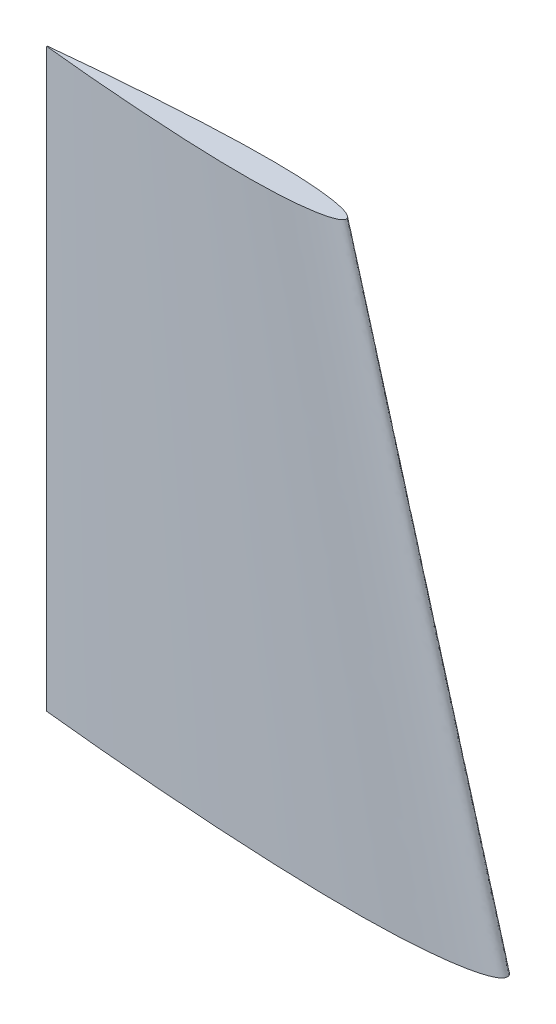
SolidWorks part; units mm, degrees
ref_plane "Front Plane" through (0, 0, 0) normal (0, 0, 1) x (1, 0, 0)
ref_plane "Top Plane" through (0, 0, 0) normal (0, 1, 0) x (1, 0, 0)
ref_plane "Right Plane" through (0, 0, 0) normal (1, 0, 0) x (0, 0, -1)
sketch "Sketch1" plane through (0, 0, 0) normal (0, 1, 0) x (1, 0, 0)
  line L0 (-150.36, 0.1421) -> (-150.36, -0.1421)
  spline S0 degree 3 poles (-150.36, 0.1421) (-150.2227, 0.1565) (-149.6751, 0.2141) (-148.4487, 0.342) (-146.4196, 0.551) (-143.6099, 0.8346) (-140.0506, 1.185) (-135.7805, 1.5925) (-130.8465, 2.0468) (-125.3025, 2.537) (-119.2094, 3.0518) (-112.6339, 3.5796) (-105.6481, 4.1088) (-98.3285, 4.6268) (-90.7552, 5.1209) (-83.0113, 5.5771) (-75.1816, 5.9812) (-67.3517, 6.3184) (-59.6075, 6.574) (-52.0337, 6.7344) (-44.7132, 6.7875) (-37.7261, 6.7242) (-31.1488, 6.5386) (-25.0534, 6.229) (-19.5062, 5.7981) (-14.5678, 5.2523) (-10.2903, 4.6034) (-6.7204, 3.8615) (-3.8842, 3.0521) (-1.8121, 2.1635) (-0.4317, 1.2454) (0.1785, 0) (-0.4317, -1.2454) (-1.8121, -2.1635) (-3.8842, -3.0521) (-6.7204, -3.8615) (-10.2903, -4.6034) (-14.5678, -5.2523) (-19.5062, -5.7981) (-25.0534, -6.229) (-31.1488, -6.5386) (-37.7261, -6.7242) (-44.7132, -6.7875) (-52.0337, -6.7344) (-59.6075, -6.574) (-67.3517, -6.3184) (-75.1816, -5.9812) (-83.0113, -5.5771) (-90.7552, -5.1209) (-98.3285, -4.6268) (-105.6481, -4.1088) (-112.6339, -3.5796) (-119.2094, -3.0518) (-125.3025, -2.537) (-130.8465, -2.0468) (-135.7805, -1.5925) (-140.0506, -1.185) (-143.6099, -0.8346) (-146.4196, -0.551) (-148.4487, -0.342) (-149.6751, -0.2141) (-150.2227, -0.1565) (-150.36, -0.1421) knots 0 0 0 0 0.001361 0.005428 0.012156 0.02147 0.033267 0.047415 0.063758 0.082114 0.102282 0.124039 0.147146 0.171348 0.196379 0.221963 0.247821 0.273669 0.299223 0.324206 0.348349 0.37139 0.393087 0.41321 0.431552 0.447929 0.462182 0.474186 0.48386 0.491199 0.496361 0.5 0.503639 0.508801 0.51614 0.525814 0.537818 0.552071 0.568448 0.58679 0.606913 0.62861 0.651651 0.675794 0.700777 0.726331 0.752179 0.778037 0.803621 0.828652 0.852854 0.875961 0.897718 0.917886 0.936242 0.952585 0.966733 0.97853 0.987844 0.994572 0.998639 1 1 1 1
ref_plane "Plane1" through (0, 187.95, 0) normal (0, 1, 0) x (1, 0, 0)
sketch "Sketch2" plane through (0, 187.95, 0) normal (0, 1, 0) x (1, 0, 0)
  line L0 (-150.36, 0.0924) -> (-150.36, -0.0924)
  spline S0 degree 3 poles (-150.36, 0.0924) (-150.2708, 0.1017) (-149.9148, 0.1392) (-149.1176, 0.2223) (-147.7987, 0.3581) (-145.9724, 0.5425) (-143.6589, 0.7702) (-140.8833, 1.0351) (-137.6762, 1.3304) (-134.0726, 1.649) (-130.1121, 1.9836) (-125.838, 2.3268) (-121.2973, 2.6707) (-116.5395, 3.0074) (-111.6169, 3.3286) (-106.5834, 3.6251) (-101.494, 3.8878) (-96.4046, 4.1069) (-91.3709, 4.2731) (-86.4479, 4.3773) (-81.6896, 4.4119) (-77.1479, 4.3707) (-72.8727, 4.2501) (-68.9107, 4.0489) (-65.3051, 3.7688) (-62.0951, 3.414) (-59.3147, 2.9922) (-56.9942, 2.51) (-55.1507, 1.9839) (-53.8039, 1.4063) (-52.9066, 0.8095) (-52.51, 0) (-52.9066, -0.8095) (-53.8039, -1.4063) (-55.1507, -1.9839) (-56.9942, -2.51) (-59.3147, -2.9922) (-62.0951, -3.414) (-65.3051, -3.7688) (-68.9107, -4.0489) (-72.8727, -4.2501) (-77.1479, -4.3707) (-81.6896, -4.4119) (-86.4479, -4.3773) (-91.3709, -4.2731) (-96.4046, -4.1069) (-101.494, -3.8878) (-106.5834, -3.6251) (-111.6169, -3.3286) (-116.5395, -3.0074) (-121.2973, -2.6707) (-125.838, -2.3268) (-130.1121, -1.9836) (-134.0726, -1.649) (-137.6762, -1.3304) (-140.8833, -1.0351) (-143.6589, -0.7702) (-145.9724, -0.5425) (-147.7987, -0.3581) (-149.1176, -0.2223) (-149.9148, -0.1392) (-150.2708, -0.1017) (-150.36, -0.0924) knots 0 0 0 0 0.001361 0.005428 0.012156 0.02147 0.033267 0.047415 0.063758 0.082114 0.102282 0.124039 0.147146 0.171348 0.196379 0.221963 0.247821 0.273669 0.299223 0.324206 0.348349 0.37139 0.393087 0.41321 0.431552 0.447929 0.462182 0.474186 0.48386 0.491199 0.496361 0.5 0.503639 0.508801 0.51614 0.525814 0.537818 0.552071 0.568448 0.58679 0.606913 0.62861 0.651651 0.675794 0.700777 0.726331 0.752179 0.778037 0.803621 0.828652 0.852854 0.875961 0.897718 0.917886 0.936242 0.952585 0.966733 0.97853 0.987844 0.994572 0.998639 1 1 1 1
loft "Loft1" add profiles "Sketch1", "Sketch2" connector at (-150.36, 0, -0.1421) connector at (-150.36, 187.95, -0.0924)
